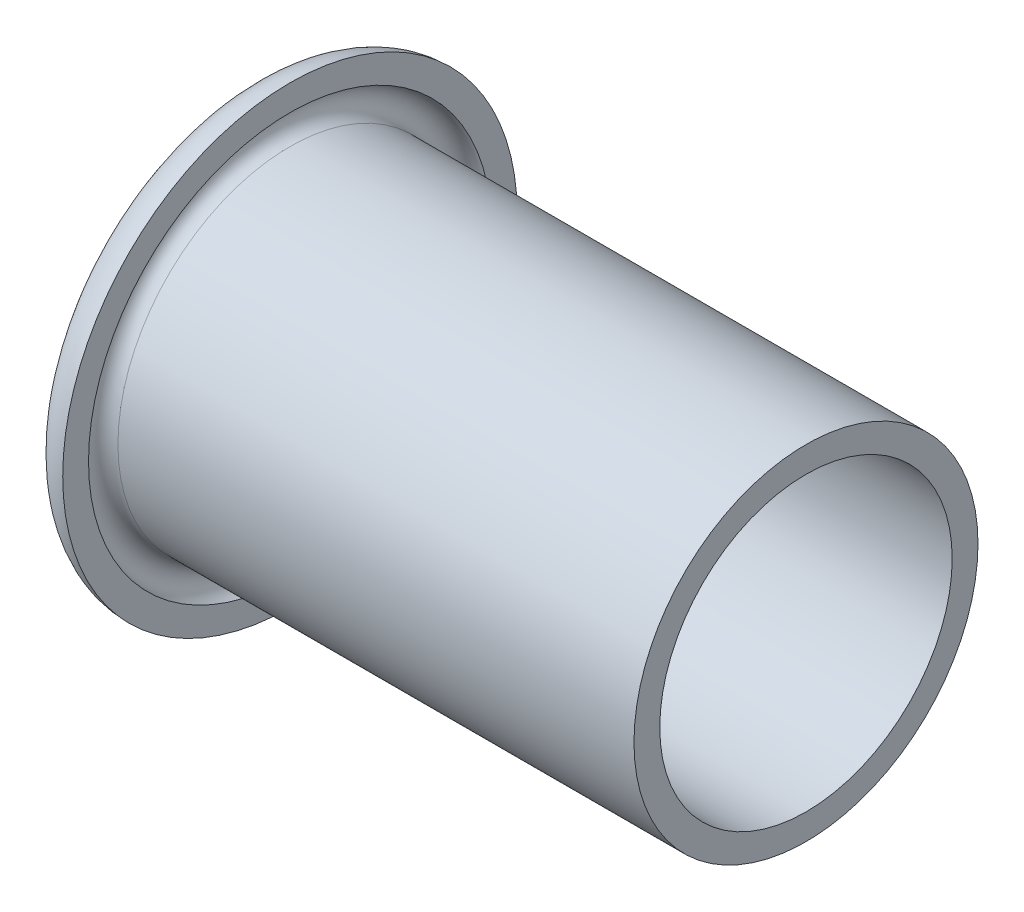
SolidWorks part; units mm, degrees
ref_plane "Front" through (0, 0, 0) normal (0, 0, 1) x (1, 0, 0)
ref_plane "Top" through (0, 0, 0) normal (0, 1, 0) x (1, 0, 0)
ref_plane "Right" through (0, 0, 0) normal (1, 0, 0) x (0, 0, -1)
sketch "Sketch1" plane through (0, 0, 0) normal (0, 0, 1) x (1, 0, 0)
  line L0 (-26.7513, 0) -> (46.6014, 0) construction
  line L1 (32.355, 8.5) -> (32.355, 10)
  line L2 (32.355, 10) -> (2.355, 10)
  line L3 (2.355, 11.71) -> (2.355, 13.21)
  line L4 (32.355, 8.5) -> (2.355, 8.5)
  line L5 (0, 10.855) -> (0, -3.4694) construction
  arc A0 (2.355, 13.21) -> (2.355, 8.5) centre (2.355, 10.855) ccw
  arc A1 (2.355, 10) -> (2.355, 11.71) centre (2.355, 10.855) cw
  dimension "dk" = 26.42
  dimension "d" = 20
  dimension "δ" = 1.5
  dimension "l" = 30
revolve "Base-Revolve" add sketch "Sketch1" angle 360 about L0
